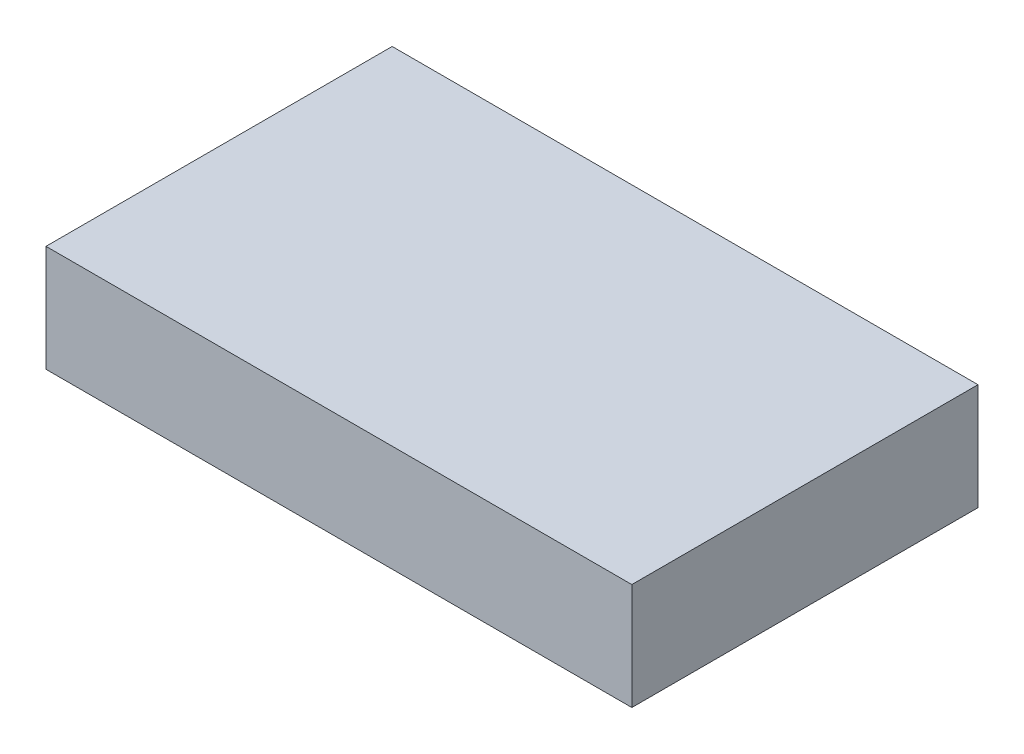
SolidWorks part; units mm, degrees
ref_plane "Front Plane" through (0, 0, 0) normal (0, 0, 1) x (1, 0, 0)
ref_plane "Top Plane" through (0, 0, 0) normal (0, 1, 0) x (1, 0, 0)
ref_plane "Right Plane" through (0, 0, 0) normal (1, 0, 0) x (0, 0, -1)
sketch "Sketch1" plane through (0, 0, 0) normal (0, 1, 0) x (1, 0, 0)
  line L1 (-11, 6.5) -> (11, 6.5)
  line L2 (-11, 6.5) -> (-11, -6.5)
  line L3 (-11, -6.5) -> (11, -6.5)
  line L4 (11, 6.5) -> (11, -6.5)
  line L5 (-11, 6.5) -> (11, -6.5) construction
  line L6 (-11, -6.5) -> (11, 6.5) construction
  point P0 (0, 0)
  dimension "D1" = 22
  dimension "D2" = 13
extrude "Boss-Extrude1" add sketch "Sketch1" along normal mid plane 4
